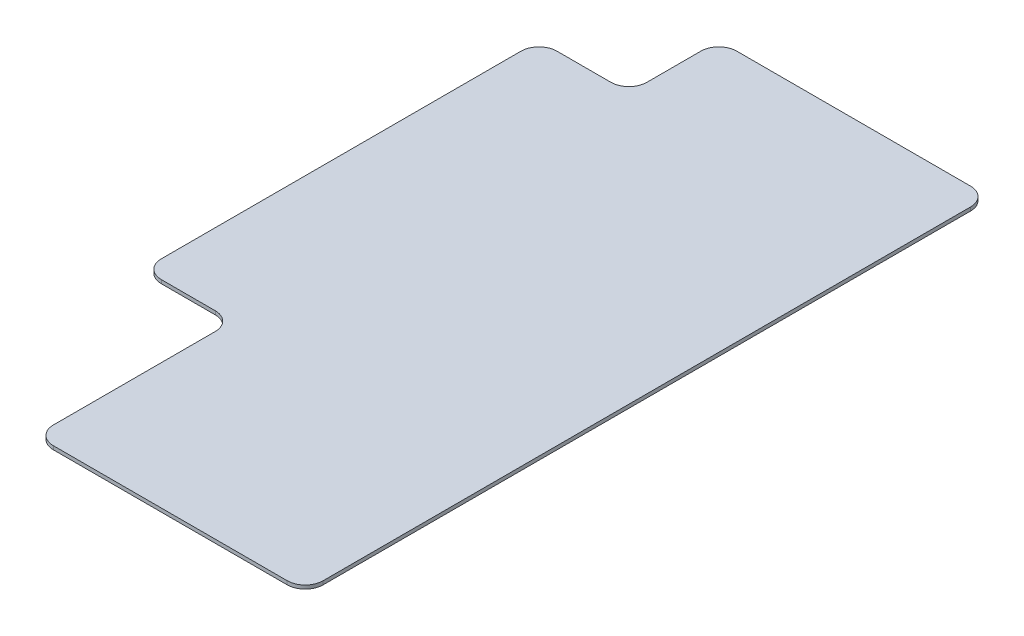
SolidWorks part; units mm, degrees
material "1.0116 (S235J2G3)"
ref_plane "Front Plane" through (0, 0, 0) normal (0, 0, 1) x (1, 0, 0)
ref_plane "Top Plane" through (0, 0, 0) normal (0, 1, 0) x (1, 0, 0)
ref_plane "Right Plane" through (0, 0, 0) normal (1, 0, 0) x (0, 0, -1)
sketch "Sketch2" plane through (0, 0, 0) normal (0, 1, 0) x (1, 0, 0)
  line L0 (-1000, 1600) -> (-1000, 600)
  line L1 (-950, 550) -> (-800, 550)
  line L2 (-750, 500) -> (-750, 50)
  line L3 (-700, 0) -> (-50, 0)
  line L4 (0, 50) -> (0, 1850)
  line L5 (-50, 1900) -> (-700, 1900)
  line L6 (-750, 1850) -> (-750, 1700)
  line L7 (-800, 1650) -> (-950, 1650)
  arc A0 (-50, 0) -> (0, 50) centre (-50, 50) ccw
  arc A1 (-750, 50) -> (-700, 0) centre (-700, 50) ccw
  arc A2 (-800, 550) -> (-750, 500) centre (-800, 500) cw
  arc A3 (-1000, 600) -> (-950, 550) centre (-950, 600) ccw
  arc A4 (-750, 1700) -> (-800, 1650) centre (-800, 1700) cw
  arc A5 (-1000, 1600) -> (-950, 1650) centre (-950, 1600) cw
  arc A6 (-700, 1900) -> (-750, 1850) centre (-700, 1850) ccw
  arc A7 (0, 1850) -> (-50, 1900) centre (-50, 1850) ccw
  point P11 (0, 0)
  point P16 (-750, 550)
  point P19 (-1000, 550)
  point P22 (-750, 1650)
  point P25 (-1000, 1650)
  point P28 (-750, 1900)
  dimension "D9" = 50
  dimension "D1" = 1000
  dimension "D2" = 1100
  dimension "D3" = 250
  dimension "D4" = 250
  dimension "D5" = 550
  dimension "D6" = 250
  dimension "D7" = 0
  dimension "D8" = 0
extrude "Boss-Extrude1" add sketch "Sketch2" along normal blind 10
